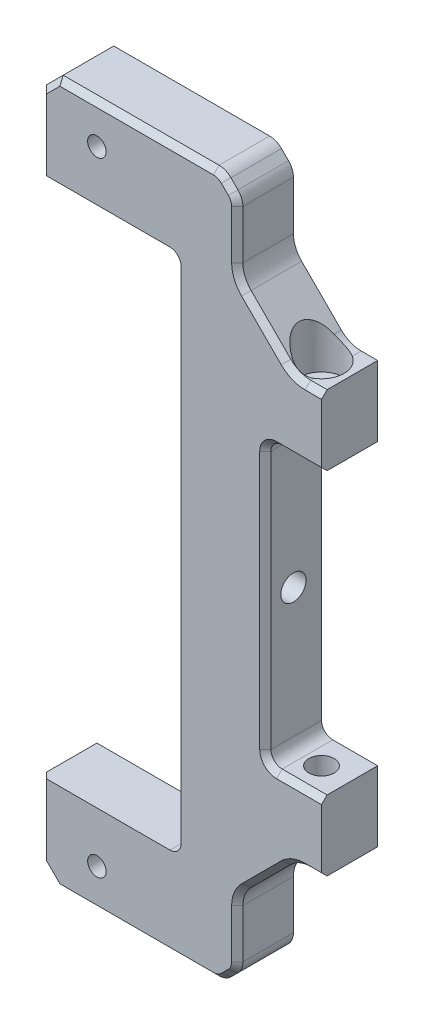
SolidWorks part; units mm, degrees
material "6061 Alloy"
ref_plane "Front Plane" through (0, 0, 0) normal (0, 0, 1) x (1, 0, 0)
ref_plane "Top Plane" through (0, 0, 0) normal (0, 1, 0) x (1, 0, 0)
ref_plane "Right Plane" through (0, 0, 0) normal (1, 0, 0) x (0, 0, -1)
sketch "Sketch1" plane through (0, 0, 0) normal (0, 0, 1) x (1, 0, 0)
  line L1 (-25, 62.5) -> (25, 62.5)
  line L2 (-25, 62.5) -> (-25, -62.5)
  line L3 (-25, -62.5) -> (25, -62.5)
  line L4 (25, 62.5) -> (25, -62.5)
  line L5 (-25, 62.5) -> (25, -62.5) construction
  line L6 (-25, -62.5) -> (25, 62.5) construction
  dimension "D1" = 125
  dimension "D2" = 50
extrude "Boss-Extrude1" add sketch "Sketch1" along normal mid plane 10 contours L3 L4 L1 L2
sketch "Sketch2" plane through (0, 0, 5) normal (0, 0, 1) x (1, 0, 0)
  line L0 (-25, 62.5) -> (-25, -62.5) construction
  line L1 (0, 46.5) -> (-25, 46.5)
  line L2 (0, 46.5) -> (0, -46.5)
  line L3 (0, -46.5) -> (-25, -46.5)
  line L4 (-25, 46.5) -> (-25, -46.5)
  line L5 (0, 46.5) -> (-25, -46.5) construction
  line L6 (0, -46.5) -> (-25, 46.5) construction
  point P0 (-12.5, 0)
  dimension "D1" = 93
  dimension "D2" = 25
extrude "Cut-Extrude1" cut sketch "Sketch2" against normal through all
sketch "Sketch3" plane through (0, 0, 5) normal (0, 0, 1) x (1, 0, 0)
  line L0 (25, 62.5) -> (25, -62.5) construction
  line L1 (15, -25) -> (25, -25)
  line L2 (15, -25) -> (15, 25)
  line L3 (15, 25) -> (25, 25)
  line L4 (25, -25) -> (25, 25)
  line L5 (15, -25) -> (25, 25) construction
  line L6 (15, 25) -> (25, -25) construction
  point P0 (20, 0)
  dimension "D1" = 50
  dimension "D2" = 10
extrude "Cut-Extrude2" cut sketch "Sketch3" against normal through all
sketch "Sketch4" plane through (0, 0, -5) normal (0, 0, -1) x (-1, 0, 0)
  line L0 (20.5, -55.5) -> (9.5, -55.5) construction
  line L1 (20.5, -57.5) -> (9.5, -57.5)
  line L2 (20.5, -53.5) -> (9.5, -53.5)
  line L3 (25, -46.5) -> (25, -62.5) construction
  line L4 (25, -62.5) -> (-25, -62.5) construction
  line L5 (5.5, 0) -> (-5.5, 0) construction
  line L6 (20.5, 55.5) -> (9.5, 55.5) construction
  line L7 (20.5, 57.5) -> (9.5, 57.5)
  line L8 (20.5, 53.5) -> (9.5, 53.5)
  arc A0 (20.5, -57.5) -> (20.5, -53.5) centre (20.5, -55.5) ccw
  arc A1 (9.5, -53.5) -> (9.5, -57.5) centre (9.5, -55.5) ccw
  arc A2 (20.5, 57.5) -> (20.5, 53.5) centre (20.5, 55.5) cw
  arc A3 (9.5, 53.5) -> (9.5, 57.5) centre (9.5, 55.5) cw
  circle A4 centre (15, -55.5) radius 3
  circle A5 centre (15, 55.5) radius 3
  point P4 (15, -55.5)
  point P10 (15, -55.5)
  point P20 (15, 55.5)
  dimension "D2" = 2
  dimension "D5" = 6
  dimension "D1" = 11
  dimension "D3" = 10
  dimension "D4" = 7
extrude "Cut-Extrude3" cut sketch "Sketch4" against normal blind 2 contours A4 L2 A1 L1 | L2 A4 L1 | L2 A4 | A4 L1 A0 L2 | L1 A4 | L8 A5 L7 A3 | A5 L7 | A5 L8 L7 | L7 A5 L8 A2 | A5 L8 region at (-19.9327, -55.5, -5) region at (-15, -57.9063, -5) region at (-15, -55.5, -5) region at (-10.0673, -55.5, -5) region at (-15, -53.0937, -5) region at (-19.9327, 55.5, -5) region at (-15, 55.5, -5) region at (-15, 57.9063, -5) region at (-10.0673, 55.5, -5) region at (-15, 53.0937, -5)
hole_wizard "M4 Tapped Hole1" positions "Sketch5" profile "Sketch6" tap size "M4" standard "GB" end condition through all
sketch "Sketch5" plane through (0, 0, -5) normal (0, 0, -1) x (-1, 0, 0)
  line L1 (25, -62.5) -> (-25, -62.5) construction
  line L2 (25, -46.5) -> (25, -62.5) construction
  line L3 (5.5, 0) -> (-5.5, 0) construction
  point P0 (15, -55.5)
  point P12 (15, 55.5)
  dimension "D1" = 7
  dimension "D2" = 10
cosmetic thread "Hole Thread1" parameters "D2"=4
cosmetic thread "Hole Thread2" parameters "D2"=4
sketch "Sketch6" plane through (-15, -55.5, -5) normal (1, 0, 0) x (0, 1, 0)
  line L0 (0, 0) -> (0, 10)
  line L1 (0, 10) -> (1.65, 10)
  line L2 (1.65, 10) -> (1.65, 0)
  line L5 (1.65, 0) -> (0, 0)
  line L11 (0, -6.35) -> (0, 107.95) construction
  dimension "Thru Tap Drill Dia." = 3.3
  dimension "Thru Tap Drill Depth" = 10
sketch "Sketch7" plane through (0, 0, -5) normal (0, 0, -1) x (-1, 0, 0)
  line L0 (5.5, 0) -> (-5.5, 0) construction
  line L1 (-25, -62.5) -> (-10, -62.5)
  line L2 (-25, -62.5) -> (-25, -37.5)
  line L3 (-25, -37.5) -> (-10, -37.5)
  line L4 (-10, -62.5) -> (-10, -37.5)
  line L5 (-25, 37.5) -> (-10, 37.5)
  line L6 (-10, 62.5) -> (-10, 37.5)
  line L7 (-25, 62.5) -> (-10, 62.5)
  line L8 (-25, 62.5) -> (-25, 37.5)
  dimension "D1" = 15
  dimension "D2" = 25
extrude "Cut-Extrude4" cut sketch "Sketch7" against normal through all
hole_wizard "CBORE for M4 Slotted cheese head screws2" positions "Sketch8" profile "Sketch9" counterbore size "M4" standard "GB" end condition through all
sketch "Sketch8" plane through (0, -37.5, 0) normal (0, -1, 0) x (-1, 0, 0)
  line L0 (-25, -5) -> (-25, 5) construction
  point P0 (-20, 0)
  dimension "D1" = 5
sketch "Sketch9" plane through (20, -37.5, 0) normal (1, 0, 0) x (0, 0, -1)
  line L0 (0, 0) -> (0, 100)
  line L1 (0, 100) -> (2.25, 100)
  line L3 (2.25, 100) -> (2.25, 4.6)
  line L4 (2.25, 4.6) -> (4, 4.6)
  line L5 (4, 4.6) -> (4, 0)
  line L7 (4, 0) -> (0, 0)
  line L11 (0, -6.35) -> (0, 107.95) construction
  dimension "Thru Hole Dia." = 4.5
  dimension "Thru Hole Depth" = 100
  dimension "C'Bore Dia." = 8
  dimension "C'Bore Depth" = 4.6
hole_wizard "CBORE for M4 Slotted cheese head screws3" positions "Sketch10" profile "Sketch11" counterbore size "M4" standard "GB" end condition through all
sketch "Sketch10" plane through (0, 0, 0) normal (-1, 0, 0) x (0, 0, 1)
  point P0 (0, 0)
sketch "Sketch11" plane through (0, 0, 0) normal (0, 1, 0) x (0, 0, 1)
  line L0 (0, 0) -> (0, 25)
  line L1 (0, 25) -> (2.25, 25)
  line L3 (2.25, 25) -> (2.25, 4.6)
  line L4 (2.25, 4.6) -> (4, 4.6)
  line L5 (4, 4.6) -> (4, 0)
  line L7 (4, 0) -> (0, 0)
  line L11 (0, -6.35) -> (0, 107.95) construction
  dimension "Thru Hole Dia." = 4.5
  dimension "Thru Hole Depth" = 25
  dimension "C'Bore Dia." = 8
  dimension "C'Bore Depth" = 4.6
mirror "Mirror1" about plane through (0, 0, 0) normal (0, 1, 0) of "CBORE for M4 Slotted cheese head screws2"
chamfer "Chamfer1" distance 10 angle 45 2 edges at (10, 37.5, 0) (10, -37.5, 0)
fillet "Fillet1" radius 5 6 edges at (10, -47.5, 0) (20, -37.5, -4.5) (10, 47.5, 0) (20, 37.5, -4.5) (20, -37.5, 4.5) (20, 37.5, 4.5)
fillet "Fillet2" radius 2 4 edges at (0, 46.5, 0) (15, 25, 0) (15, -25, 0) (0, -46.5, 0)
chamfer "Chamfer2" distance 3 angle 45 4 edges at (10, -62.5, 0) (10, 62.5, 0) (-25, -62.5, 0) (-25, 62.5, 0)
fillet "Fillet3" radius 3 4 edges at (7, 62.5, 0) (10, 59.5, 0) (10, -59.5, 0) (7, -62.5, 0)
chamfer "Chamfer3" distance 1 angle 45 27 edges at (-8.1213, -62.5, 5) (6.9054, -62.2716, 5) (8.5, -61, 5) (9.7716, -59.4054, 5) (10, -53.9142, 5) (23.5355, -37.5, 5) (10.3806, -47.6577, 5) (20.1577, -37.8806, 5) (15, -42.5, 5) (-8.1213, 62.5, 5) (6.9054, 62.2716, 5) (8.5, 61, 5) (9.7716, 59.4054, 5) (23.5355, 37.5, 5) (10, 53.9142, 5) (20.1577, 37.8806, 5) (10.3806, 47.6577, 5) (15, 42.5, 5) (21, 25, 5) (21, -25, 5) (15.5858, 24.4142, 5) (15.5858, -24.4142, 5) (15, 0, 5) (-23.5, 61, 5) (-25, 53, 5) (-25, -53, 5) (-23.5, -61, 5)
